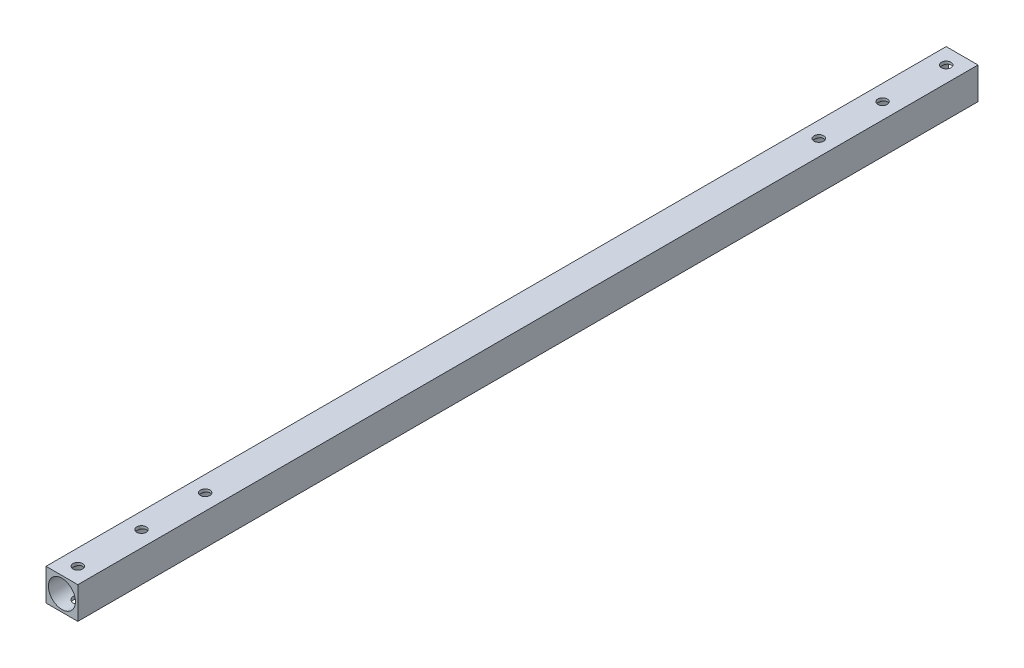
SolidWorks part; units mm, degrees
material "Thornel VCB-20 Carbon Cloth"
ref_plane "Front Plane" through (0, 0, 0) normal (0, 0, 1) x (1, 0, 0)
ref_plane "Top Plane" through (0, 0, 0) normal (0, 1, 0) x (1, 0, 0)
ref_plane "Right Plane" through (0, 0, 0) normal (1, 0, 0) x (0, 0, -1)
sketch "Sketch1" plane through (0, 0, 0) normal (0, 0, 1) x (1, 0, 0)
  line L1 (-5, -5) -> (5, -5)
  line L2 (-5, -5) -> (-5, 5)
  line L3 (-5, 5) -> (5, 5)
  line L4 (5, -5) -> (5, 5)
  line L5 (-5, -5) -> (5, 5) construction
  line L6 (-5, 5) -> (5, -5) construction
  circle A0 centre (0, 0) radius 4.25
  point P0 (0, 0)
  dimension "D3" = 8.5
  dimension "D1" = 10
  dimension "D2" = 10
extrude "Boss-Extrude1" add sketch "Sketch1" along normal blind 282.8
sketch "Sketch2" plane through (0, 5, 0) normal (0, 1, 0) x (1, 0, 0)
  line L0 (0, 0) -> (0, -5) construction
  line L1 (5, 0) -> (-5, 0) construction
  line L2 (0, -5) -> (0, -25) construction
  line L3 (0, -25) -> (0, -45) construction
  line L4 (0, -282.8) -> (0, -277.8) construction
  line L5 (5, -282.8) -> (-5, -282.8) construction
  line L6 (0, -277.8) -> (0, -257.8) construction
  line L7 (0, -257.8) -> (0, -237.8) construction
  circle A0 centre (0, -5) radius 1.5
  circle A1 centre (0, -25) radius 1.5
  circle A2 centre (0, -45) radius 1.5
  circle A3 centre (0, -277.8) radius 1.5
  circle A4 centre (0, -257.8) radius 1.5
  circle A5 centre (0, -237.8) radius 1.5
  dimension "D3" = 3
  dimension "D6" = 3
  dimension "D1" = 20
  dimension "D2" = 5
  dimension "D4" = 20
  dimension "D5" = 5
extrude "Cut-Extrude1" cut sketch "Sketch2" against normal through all
